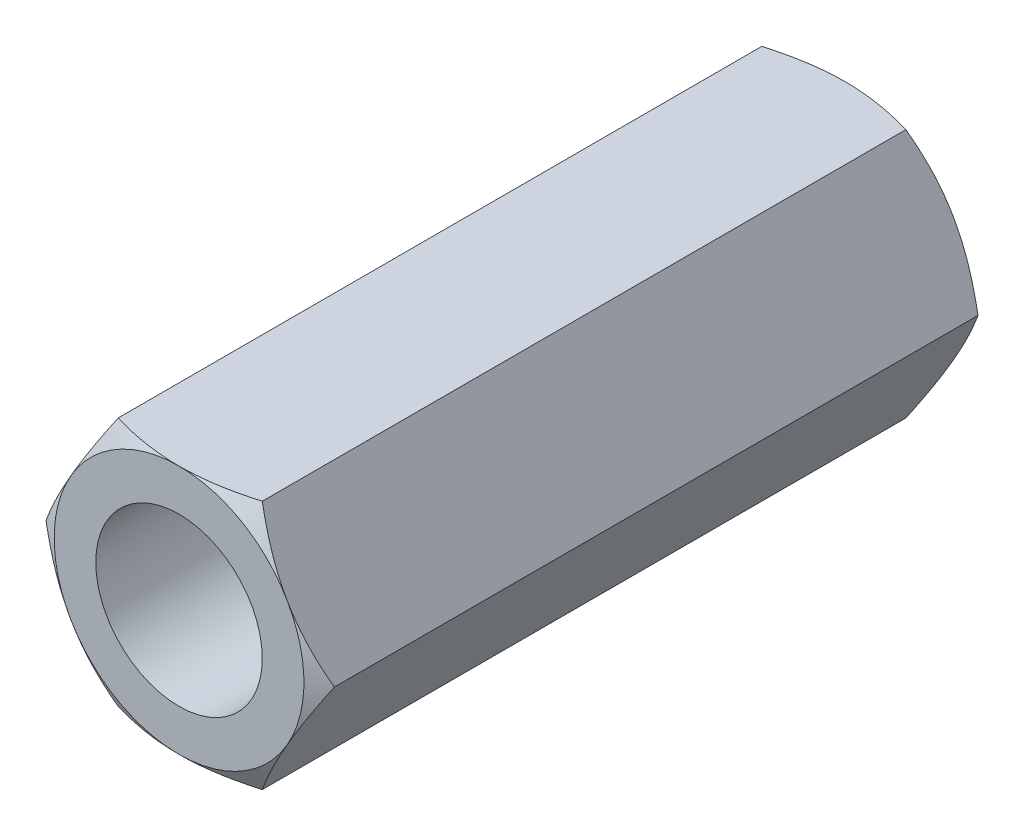
SolidWorks part; units mm, degrees
material "AL 6061-T6"
ref_plane "Front Plane" through (0, 0, 0) normal (0, 0, 1) x (1, 0, 0)
ref_plane "Top Plane" through (0, 0, 0) normal (0, 1, 0) x (1, 0, 0)
ref_plane "Right Plane" through (0, 0, 0) normal (1, 0, 0) x (0, 0, -1)
ref_axis "Axis1" through (0, 0, -52.8182) along (0, 0, 1)
ref_axis "Axis2" through (0, -15.5981, 0) along (0, 1, 0)
ref_axis "Axis3" through (-12.2581, 0, 0) along (1, 0, 0)
sketch "Sketch1" plane through (0, 0, 0) normal (1, 0, 0) x (0, 0, -1)
  line L0 (-8, 0) -> (-8, 3)
  line L1 (-7.567, 3.75) -> (7.567, 3.75)
  line L2 (8, 3) -> (8, 0)
  line L3 (-8, 3) -> (-7.567, 3.75)
  line L4 (0, 0) -> (0, 3.75) construction
  line L5 (8, 0) -> (-8, 0)
  line L6 (-5.5849, 0) -> (13.8966, 0) construction
  line L7 (8, 3) -> (7.567, 3.75)
  dimension "D1" = 30
  dimension "D2" = 7.5
  dimension "D3" = 6
  dimension "LENGTH" = 16
revolve "Revolve1" add sketch "Sketch1" angle 360 about L6
sketch "Sketch2" plane through (0, 0, 8) normal (0, 0, 1) x (1, 0, 0)
  line L1 (1.7321, -3) -> (3.4641, 0)
  line L2 (3.4641, 0) -> (1.7321, 3)
  line L3 (1.7321, 3) -> (-1.7321, 3)
  line L4 (-1.7321, 3) -> (-3.4641, 0)
  line L5 (-3.4641, 0) -> (-1.7321, -3)
  line L6 (-1.7321, -3) -> (1.7321, -3)
  circle A0 centre (0, 0) radius 3 construction
  dimension "D1" = 6
extrude "Cut-Extrude1" cut sketch "Sketch2" against normal through all flip side to cut
hole_wizard "M4x0.7 Tapped Hole1" positions "Sketch4" profile "Sketch3" tap size "M4x0.7" standard "ANSI Metric"
sketch "Sketch4" plane through (0, 0, 8) normal (0, 0, 1) x (1, 0, 0)
  point P0 (0, 0)
sketch "Sketch3" plane through (0, 0, 8) normal (1, 0, 0) x (0, -1, 0)
  line L0 (0, 0) -> (0, 15.4914)
  line L1 (0, 15.4914) -> (1.65, 14.5)
  line L2 (1.65, 14.5) -> (1.65, 13.1)
  line L3 (1.65, 13.1) -> (2, 13.1)
  line L4 (2, 13.1) -> (2, 0)
  line L5 (2, 0) -> (0, 0)
  line L10 (0, 15.4914) -> (-1.65, 14.5) construction
  line L11 (0, -6.35) -> (0, 107.95) construction
  dimension "Tap Drill Dia." = 3.3
  dimension "Tap Drill Depth" = 14.5
  dimension "Thread Major Dia." = 4
  dimension "Thread Depth" = 13.1
  dimension "Drill Angle" = 118
hole_wizard "M4x0.7 Tapped Hole2" positions "Sketch6" profile "Sketch5" tap size "M4x0.7" standard "ANSI Metric"
sketch "Sketch6" plane through (0, 0, -8) normal (0, 0, -1) x (-1, 0, 0)
  point P0 (0, 0)
sketch "Sketch5" plane through (0, 0, -8) normal (1, 0, 0) x (0, 1, 0)
  line L0 (0, 0) -> (0, 13.4914)
  line L1 (0, 13.4914) -> (1.65, 12.5)
  line L2 (1.65, 12.5) -> (1.65, 11.1)
  line L3 (1.65, 11.1) -> (2, 11.1)
  line L4 (2, 11.1) -> (2, 0)
  line L5 (2, 0) -> (0, 0)
  line L10 (0, 13.4914) -> (-1.65, 12.5) construction
  line L11 (0, -6.35) -> (0, 107.95) construction
  dimension "Tap Drill Dia." = 3.3
  dimension "Tap Drill Depth" = 12.5
  dimension "Thread Major Dia." = 4
  dimension "Thread Depth" = 11.1
  dimension "Drill Angle" = 118
